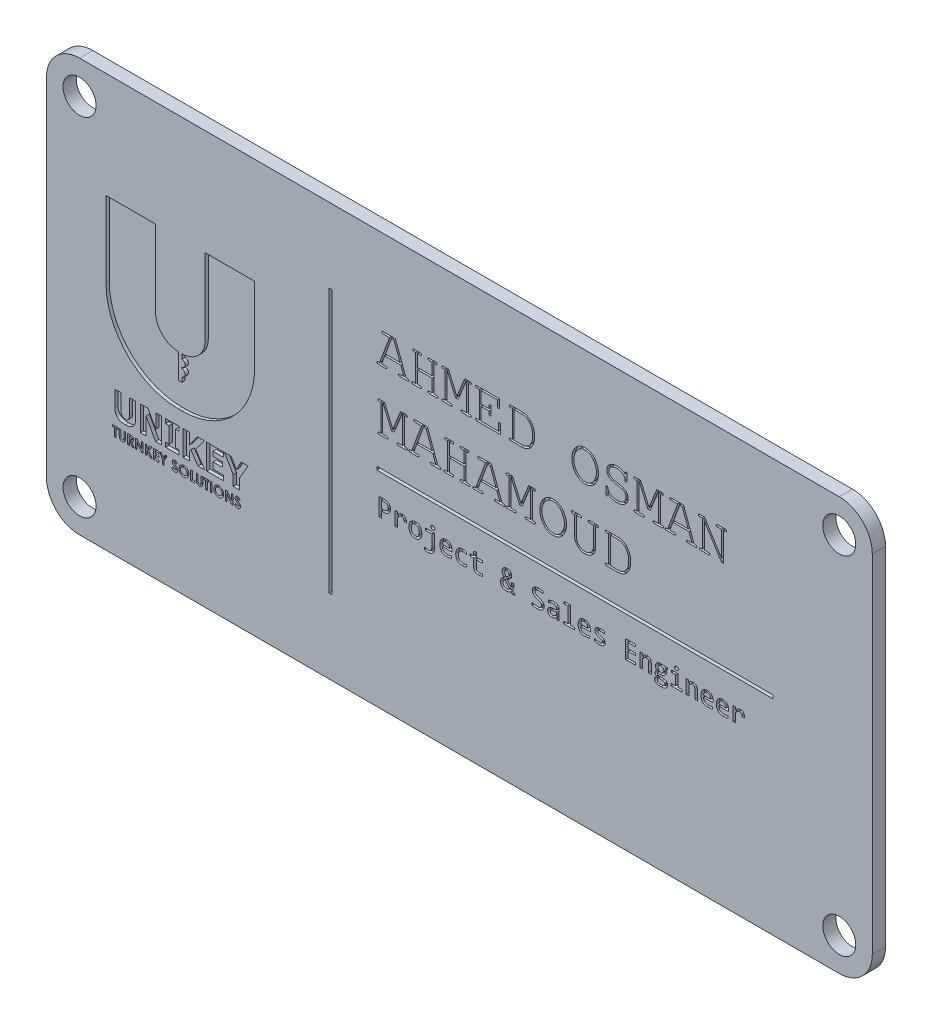
SolidWorks part; units mm, degrees
ref_plane "Front Plane" through (0, 0, 0) normal (0, 0, 1) x (1, 0, 0)
ref_plane "Top Plane" through (0, 0, 0) normal (0, 1, 0) x (1, 0, 0)
ref_plane "Right Plane" through (0, 0, 0) normal (1, 0, 0) x (0, 0, -1)
sketch "Sketch1" plane through (0, 0, 0) normal (0, 0, 1) x (1, 0, 0)
  line L1 (-138.3285, 38.6455) -> (91.6715, 38.6455)
  line L2 (-148.3285, 28.6455) -> (-148.3285, -76.3545)
  line L3 (-138.3285, -86.3545) -> (91.6715, -86.3545)
  line L4 (101.6715, 28.6455) -> (101.6715, -76.3545)
  arc A0 (-138.3285, 38.6455) -> (-148.3285, 28.6455) centre (-138.3285, 28.6455) ccw
  arc A1 (-148.3285, -76.3545) -> (-138.3285, -86.3545) centre (-138.3285, -76.3545) ccw
  arc A2 (91.6715, -86.3545) -> (101.6715, -76.3545) centre (91.6715, -76.3545) ccw
  arc A3 (91.6715, 38.6455) -> (101.6715, 28.6455) centre (91.6715, 28.6455) cw
  circle A4 centre (-138.3285, 28.6455) radius 5
  circle A5 centre (91.6715, 28.6455) radius 5
  circle A6 centre (91.6715, -76.3545) radius 5
  circle A7 centre (-138.3285, -76.3545) radius 5
  point P6 (-148.3285, 38.6455)
  point P11 (101.6715, -86.3545)
  point P14 (101.6715, 38.6455)
  dimension "D3" = 10
  dimension "D4" = 10
  dimension "D1" = 250
  dimension "D2" = 125
extrude "Boss-Extrude1" add sketch "Sketch1" against normal blind 4
sketch "Sketch2" plane through (0, 0, 0) normal (0, 0, 1) x (1, 0, 0)
  line L0 (-138.3285, -86.3545) -> (91.6715, -86.3545) construction
  line L1 (-62.8285, 16.1455) -> (-61.8285, 16.1455)
  line L2 (-62.8285, 16.1455) -> (-62.8285, -63.8545)
  line L3 (-62.8285, -63.8545) -> (-61.8285, -63.8545)
  line L4 (-61.8285, 16.1455) -> (-61.8285, -63.8545)
  line L5 (-115.3285, 6.6455) -> (-115.3285, -16.3545)
  line L6 (-130.3285, 6.6455) -> (-115.3285, 6.6455)
  line L7 (-130.3285, 6.6455) -> (-130.3285, -16.3545)
  line L8 (-108.3285, -38.3545) -> (-107.3285, -38.3545)
  line L9 (-85.3285, 6.6455) -> (-85.3285, -16.3545)
  line L11 (-100.3285, 6.6455) -> (-100.3285, -16.3545)
  line L13 (-115.3285, -8.3545) -> (-100.3285, -8.3545) construction
  line L14 (-115.3285, -8.3545) -> (-115.3285, -16.3545) construction
  line L15 (-100.3285, -8.3545) -> (-100.3285, -16.3545) construction
  line L16 (-107.3285, -29.3545) -> (-107.3285, -30.8545)
  line L18 (-108.3285, -23.3545) -> (-108.3285, -30.8545)
  line L19 (-108.3285, -30.8545) -> (-107.3285, -30.8545)
  line L20 (-107.3285, -23.3545) -> (-107.3285, -24.8545)
  line L21 (-108.3285, -23.3545) -> (-107.3285, -23.3545) construction
  line L22 (-107.3285, -26.8545) -> (-107.3285, -27.3545)
  line L23 (-100.3285, 6.6455) -> (-85.3285, 6.6455)
  line L24 (-130.3285, 6.6455) -> (-85.3285, 6.6455) construction
  line L25 (-148.3285, 28.6455) -> (-148.3285, -76.3545) construction
  line L26 (91.6715, 38.6455) -> (-138.3285, 38.6455) construction
  line L28 (-48.3285, -24.3545) -> (71.6715, -24.3545)
  line L29 (-48.3285, -24.3545) -> (-48.3285, -23.3545)
  line L30 (-48.3285, -23.3545) -> (71.6715, -23.3545)
  line L31 (71.6715, -24.3545) -> (71.6715, -23.3545)
  line L32 (-48.3285, -24.3545) -> (71.6715, -23.3545) construction
  line L33 (-48.3285, -23.3545) -> (71.6715, -24.3545) construction
  arc A0 (-107.3285, -38.3545) -> (-85.3285, -16.3545) centre (-107.3285, -16.3545) ccw
  arc A1 (-130.3285, -16.3545) -> (-108.3285, -38.3545) centre (-108.3285, -16.3545) ccw
  arc A2 (-115.3285, -16.3545) -> (-108.3285, -23.3545) centre (-108.3285, -16.3545) ccw
  arc A3 (-107.3285, -23.3545) -> (-100.3285, -16.3545) centre (-107.3285, -16.3545) ccw
  arc A4 (-107.3285, -26.8545) -> (-107.3285, -24.8545) centre (-107.3285, -25.8545) ccw
  arc A5 (-107.3285, -29.3545) -> (-107.3285, -27.3545) centre (-107.3285, -28.3545) ccw
  text T0 "AHMED OSMAN \r\nMAHAMOUD" font "Courier New" height in points 36
  text T1 "Project & Sales Engineer" font "Consolas" height in points 20
  text T2 "<b>UNIKEY</b>" font "Tahoma" height in points 28
  text T3 "<b>TURNKEY SOLUTIONS</b>" font "Century Gothic" height in points 11
  point P4 (-62.8285, -23.8545)
  point P33 (11.6715, -23.8545)
  dimension "D6" = 22
  dimension "D1" = 1
  dimension "D2" = 80
  dimension "D3" = 62.5
  dimension "D4" = 45
  dimension "D8" = 2.5
  dimension "D9" = 2.5
  dimension "D7" = 40
  dimension "D10" = 70
  dimension "D11" = 45
  dimension "D12" = 7.5
  dimension "D13" = 85.5
  dimension "D14" = 35
  dimension "D15" = 100
  dimension "D16" = 1
  dimension "D17" = 120
  dimension "D18" = 100
  dimension "D19" = 62.5
  dimension "D20" = 50
  dimension "D21" = 0
  dimension "D22" = 5
  dimension "D23" = 12
  dimension "D24" = 20
  dimension "D5" = 15
extrude "Cut-Extrude1" cut sketch "Sketch2" against normal blind 1
equation "\"D3@Sketch2\"=125/2"
